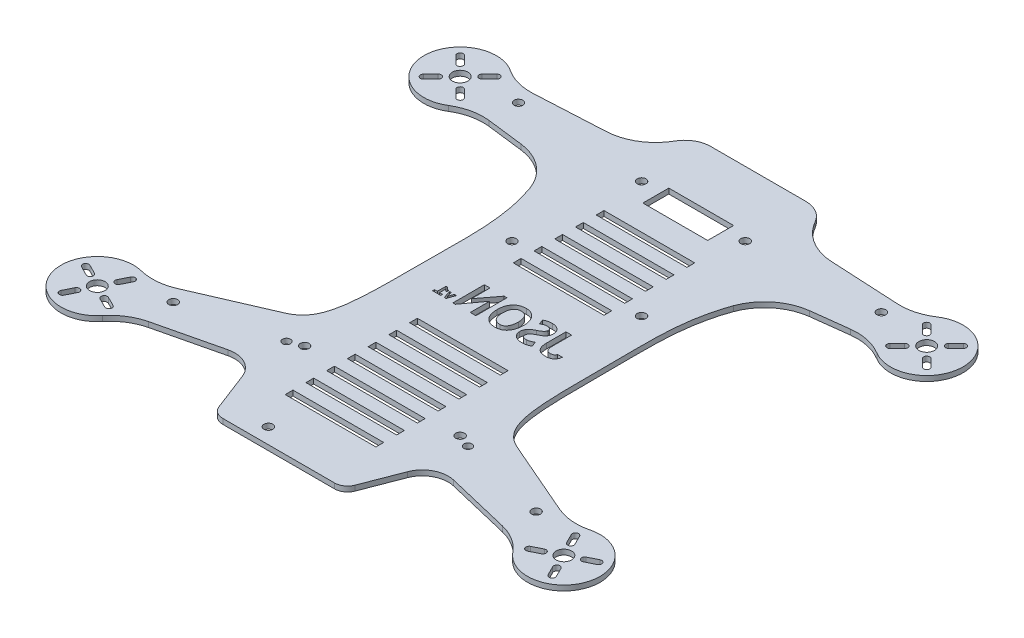
SolidWorks part; units mm, degrees
ref_plane "Front Plane" through (0, 0, 0) normal (0, 0, 1) x (1, 0, 0)
ref_plane "Top Plane" through (0, 0, 0) normal (0, 1, 0) x (1, 0, 0)
ref_plane "Right Plane" through (0, 0, 0) normal (1, 0, 0) x (0, 0, -1)
sketch "Sketch1" plane through (0, 0, 0) normal (0, 1, 0) x (1, 0, 0)
  line L0 (0, 0) -> (0, -50170.9215) construction
  line L1 (-78.5109, 78) -> (-25, 80.8044)
  line L2 (-25, 80.8044) -> (-25, 95)
  line L3 (-25, 95) -> (25, 95)
  line L4 (-144.3888, -88.1296) -> (-47556.2899, -15892.0966) construction
  line L5 (-120, 70) -> (49880, 70) construction
  line L6 (-78.5109, 62) -> (-45, 57.8854)
  line L7 (-45, -42.8995) -> (-81.6303, -58.7774)
  line L8 (-76.5706, -73.9563) -> (-35, -64.026)
  line L9 (-35, -64.026) -> (-25, -90)
  line L10 (-25, -90) -> (25, -90)
  line L11 (-35, -22.0249) -> (-35, 13.8306) construction
  line L12 (35, -64.026) -> (25, -90)
  line L13 (76.5706, -73.9563) -> (35, -64.026)
  line L14 (45, -42.8995) -> (81.6303, -58.7774)
  line L15 (78.5109, 62) -> (45, 57.8854)
  line L16 (25, 80.8044) -> (25, 95)
  line L17 (78.5109, 78) -> (25, 80.8044)
  arc A0 (-78.5109, 78) -> (-78.5109, 62) centre (-90, 70) ccw
  arc A1 (81.6303, -58.7774) -> (76.5706, -73.9563) centre (90, -70) cw
  arc A2 (-81.6303, -58.7774) -> (-76.5706, -73.9563) centre (-90, -70) ccw
  arc A4 (78.5109, 78) -> (78.5109, 62) centre (90, 70) cw
  spline S0 degree 3 poles (-45, 57.8854) (-33.8617, 40.1769) (-35.1319, 16.9314) (-34.8096, -29.2686) (-36.3436, -39.1473) (-45, -42.8995) knots 0 0 0 0 0.350758 0.450758 1 1 1 1
  spline S1 degree 3 poles (45, 57.8854) (33.8617, 40.1769) (35.1319, 16.9314) (34.8096, -29.2686) (36.3436, -39.1473) (45, -42.8995) knots 0 0 0 0 0.350758 0.450758 1 1 1 1
  point P2 (0, -40)
  point P48 (0, -90)
  point P49 (0, -90)
  point P51 (0, -90)
  point P52 (0, 95)
  dimension "D1" = 90
  dimension "D2" = 28
  dimension "D3" = 25
  dimension "D4" = 3
  dimension "D5" = 70
  dimension "D6" = 35
  dimension "D7" = 25
  dimension "D8" = 8
  dimension "D9" = 10
  dimension "D10" = 70
  dimension "D11" = 40
  dimension "D12" = 8
  dimension "D13" = 45
  dimension "D14" = 90
  dimension "D15" = 10
  dimension "D16" = 45
  dimension "D17" = 25
  dimension "D18" = 5
  dimension "D19" = 35
extrude "Boss-Extrude1" add sketch "Sketch1" along normal blind 2
fillet "Fillet1" radius 20 2 edges at (25, 1, -80.8044) (-25, 1, -80.8044)
fillet "Fillet2" radius 10 2 edges at (-25, 1, -95) (25, 1, -95)
fillet "Fillet3" radius 20 10 edges at (76.5706, 1, 73.9563) (81.6303, 1, 58.7774) (-81.6303, 1, 58.7774) (-76.5706, 1, 73.9563) (78.5109, 1, -78) (78.5109, 1, -62) (45, 1, -57.8854) (-45, 1, -57.8854) (-78.5109, 1, -78) (-78.5109, 1, -62)
fillet "Fillet4" radius 10 2 edges at (35, 1, 64.026) (-35, 1, 64.026)
sketch "Sketch2" plane through (0, 2, 0) normal (0, 1, 0) x (1, 0, 0)
  line L0 (-100, 70) -> (-50100, 70) construction
  line L1 (-95, 65) -> (-35450.3391, -35290.3391) construction
  line L2 (-97.0711, 62.9289) -> (-94.2426, 65.7574) construction
  line L3 (-97.9196, 63.7775) -> (-95.0912, 66.6059)
  line L4 (-96.2225, 62.0804) -> (-93.3941, 64.9088)
  arc A0 (-97.9196, 63.7775) -> (-96.2225, 62.0804) centre (-97.0711, 62.9289) ccw
  arc A1 (-93.3941, 64.9088) -> (-95.0912, 66.6059) centre (-94.2426, 65.7574) ccw
  point P7 (-95.6569, 64.3431)
  point P12 (-90, 70)
  dimension "D1" = 45
  dimension "D2" = 4
  dimension "D3" = 8
  dimension "D4" = 2.4
extrude "Cut-Extrude1" cut sketch "Sketch2" against normal through all
sketch "Sketch4" plane through (0, 2, 0) normal (0, 1, 0) x (1, 0, 0)
  line L0 (-99, -73) -> (-47511.4011, -15877.1337) construction
  line L1 (-92, -74) -> (-22442.4202, -44774.8405) construction
  line L2 (-92.6833, -75.3666) -> (-94.4721, -78.9443) construction
  line L3 (-91.61, -75.9032) -> (-93.3988, -79.4809)
  line L4 (-93.7566, -74.8299) -> (-95.5454, -78.4076)
  arc A0 (-91.61, -75.9032) -> (-93.7566, -74.8299) centre (-92.6833, -75.3666) ccw
  arc A1 (-95.5454, -78.4076) -> (-93.3988, -79.4809) centre (-94.4721, -78.9443) ccw
  point P9 (-93.5777, -77.1554)
  point P14 (-92.5044, -77.6921)
  point P15 (-90, -70)
  dimension "D1" = 45
  dimension "D2" = 2.4
  dimension "D3" = 4
  dimension "D4" = 8
extrude "Cut-Extrude3" cut sketch "Sketch4" against normal through all
sketch "Sketch3" plane through (0, 2, 0) normal (0, 1, 0) x (1, 0, 0)
  circle A0 centre (-90, 70) radius 3
  circle A1 centre (-90, -70) radius 3
  dimension "D1" = 6
extrude "Cut-Extrude2" cut sketch "Sketch3" against normal through all
pattern_circular "CirPattern1" count 4 over 360 about axis through (-90, 2, -70) along (0, -1, 0) of "Cut-Extrude1"
pattern_circular "CirPattern2" count 4 over 360 about axis through (-90, 2, 70) along (0, -1, 0) of "Cut-Extrude3"
mirror "Mirror1" about plane through (0, 0, 0) normal (1, 0, 0) of "CirPattern2", "Cut-Extrude2", "CirPattern1"
sketch "Sketch5" plane through (0, 2, 0) normal (0, 1, 0) x (1, 0, 0)
  line L0 (-100, 70) -> (-50050.7788, 70) construction
  line L1 (0, 0) -> (0, -50000) construction
  line L2 (-99, -73) -> (-47511.4011, -15877.1337) construction
  line L3 (-25, -90) -> (25, -90) construction
  circle A0 centre (-70, 72.5) radius 1.7
  circle A1 centre (-70, -60.6981) radius 1.7
  circle A2 centre (70, -60.6981) radius 1.7
  circle A3 centre (70, 72.5) radius 1.7
  circle A4 centre (-20, 70) radius 1.7
  circle A5 centre (-30, -50) radius 1.7
  circle A6 centre (30, -50) radius 1.7
  circle A7 centre (20, 70) radius 1.7
  circle A8 centre (-25, 25) radius 1.7
  circle A9 centre (25, 25) radius 1.7
  circle A10 centre (-10, -84) radius 1.7
  dimension "D1" = 3.4
  dimension "D4" = 20
  dimension "D3" = 25
  dimension "D9" = 10
  dimension "D2" = 70
  dimension "D5" = 25
  dimension "D6" = 30
  dimension "D7" = 2.5
  dimension "D8" = 2.5
  dimension "D10" = 6
extrude "Cut-Extrude4" cut sketch "Sketch5" against normal through all
sketch "Sketch6" plane through (0, 2, 0) normal (0, 1, 0) x (1, 0, 0)
  line L1 (-12.5, 73) -> (12.5, 73)
  line L2 (-12.5, 73) -> (-12.5, 63)
  line L3 (-12.5, 63) -> (12.5, 63)
  line L4 (12.5, 73) -> (12.5, 63)
  line L5 (-12.5, 73) -> (12.5, 63) construction
  line L6 (-12.5, 63) -> (12.5, 73) construction
  point P0 (0, 68)
  dimension "D1" = 25
  dimension "D2" = 10
  dimension "D3" = 63
extrude "Cut-Extrude5" cut sketch "Sketch6" against normal through all
fillet "Fillet5" radius 5 2 edges at (25, 1, 90) (-25, 1, 90)
sketch "Sketch7" plane through (0, 0, 0) normal (0, 1, 0) x (1, 0, 0)
  line L0 (0, 0) -> (0, -50000) construction
  line L1 (-17.5, 45) -> (17.5, 45)
  line L2 (-17.5, 53) -> (17.5, 53)
  line L3 (-17.5, 53) -> (-17.5, 50)
  line L4 (-17.5, 50) -> (17.5, 50)
  line L5 (17.5, 53) -> (17.5, 50)
  line L6 (-17.5, 45) -> (-17.5, 42)
  line L7 (-17.5, 42) -> (17.5, 42)
  line L8 (17.5, 45) -> (17.5, 42)
  line L9 (-17.5, 37) -> (17.5, 37)
  line L10 (-17.5, 37) -> (-17.5, 34)
  line L11 (-17.5, 34) -> (17.5, 34)
  line L12 (17.5, 37) -> (17.5, 34)
  line L13 (-17.5, 29) -> (17.5, 29)
  line L14 (-17.5, 29) -> (-17.5, 26)
  line L15 (-17.5, 26) -> (17.5, 26)
  line L16 (17.5, 29) -> (17.5, 26)
  line L17 (-17.5, 21) -> (17.5, 21)
  line L18 (-17.5, 21) -> (-17.5, 18)
  line L19 (-17.5, 18) -> (17.5, 18)
  line L20 (17.5, 21) -> (17.5, 18)
  line L21 (-17.5, 13) -> (17.5, 13) [skipped]
  line L22 (-17.5, 13) -> (-17.5, 10) [skipped]
  line L23 (-17.5, 10) -> (17.5, 10) [skipped]
  line L24 (17.5, 13) -> (17.5, 10) [skipped]
  line L25 (-17.5, 5) -> (17.5, 5) [skipped]
  line L26 (-17.5, 5) -> (-17.5, 2) [skipped]
  line L27 (-17.5, 2) -> (17.5, 2) [skipped]
  line L28 (17.5, 5) -> (17.5, 2) [skipped]
  line L29 (-17.5, -3) -> (17.5, -3) [skipped]
  line L30 (-17.5, -3) -> (-17.5, -6) [skipped]
  line L31 (-17.5, -6) -> (17.5, -6) [skipped]
  line L32 (17.5, -3) -> (17.5, -6) [skipped]
  line L33 (-17.5, -11) -> (17.5, -11) [skipped]
  line L34 (-17.5, -11) -> (-17.5, -14) [skipped]
  line L35 (-17.5, -14) -> (17.5, -14) [skipped]
  line L36 (17.5, -11) -> (17.5, -14) [skipped]
  line L37 (-17.5, -19) -> (17.5, -19)
  line L38 (-17.5, -19) -> (-17.5, -22)
  line L39 (-17.5, -22) -> (17.5, -22)
  line L40 (17.5, -19) -> (17.5, -22)
  line L41 (-17.5, -27) -> (17.5, -27)
  line L42 (-17.5, -27) -> (-17.5, -30)
  line L43 (-17.5, -30) -> (17.5, -30)
  line L44 (17.5, -27) -> (17.5, -30)
  line L45 (-17.5, -35) -> (17.5, -35)
  line L46 (-17.5, -35) -> (-17.5, -38)
  line L47 (-17.5, -38) -> (17.5, -38)
  line L48 (17.5, -35) -> (17.5, -38)
  line L49 (-17.5, -43) -> (17.5, -43)
  line L50 (-17.5, -43) -> (-17.5, -46)
  line L51 (-17.5, -46) -> (17.5, -46)
  line L52 (17.5, -43) -> (17.5, -46)
  line L53 (-17.5, -51) -> (17.5, -51)
  line L54 (-17.5, -51) -> (-17.5, -54)
  line L55 (-17.5, -54) -> (17.5, -54)
  line L56 (17.5, -51) -> (17.5, -54)
  line L57 (-17.5, -59) -> (17.5, -59)
  line L58 (-17.5, -59) -> (-17.5, -62)
  line L59 (-17.5, -62) -> (17.5, -62)
  line L60 (17.5, -59) -> (17.5, -62)
  line L61 (-17.5, -67) -> (17.5, -67)
  line L62 (-17.5, -67) -> (-17.5, -70)
  line L63 (-17.5, -70) -> (17.5, -70)
  line L64 (17.5, -67) -> (17.5, -70)
  text T0 "JSON" font "Trebuchet MS" height 12
  text T1 "<b>v1</b>" font "Franklin Gothic Medium" height 4
  dimension "D1" = 35
  dimension "D2" = 3
  dimension "D3" = 50
  dimension "D5" = 8
  dimension "D4" = 16
extrude "Cut-Extrude6" cut sketch "Sketch7" along normal through all
sketch "Sketch8" plane through (0, 2, 0) normal (0, 1, 0) x (1, 0, 0)
  line L0 (0, 0) -> (0, -50000) construction
  circle A0 centre (-35, -52) radius 1.55
  circle A1 centre (35, -52) radius 1.55
  dimension "D1" = 3.1
  dimension "D2" = 35
  dimension "D3" = 52
extrude "Cut-Extrude7" cut sketch "Sketch8" against normal through all
